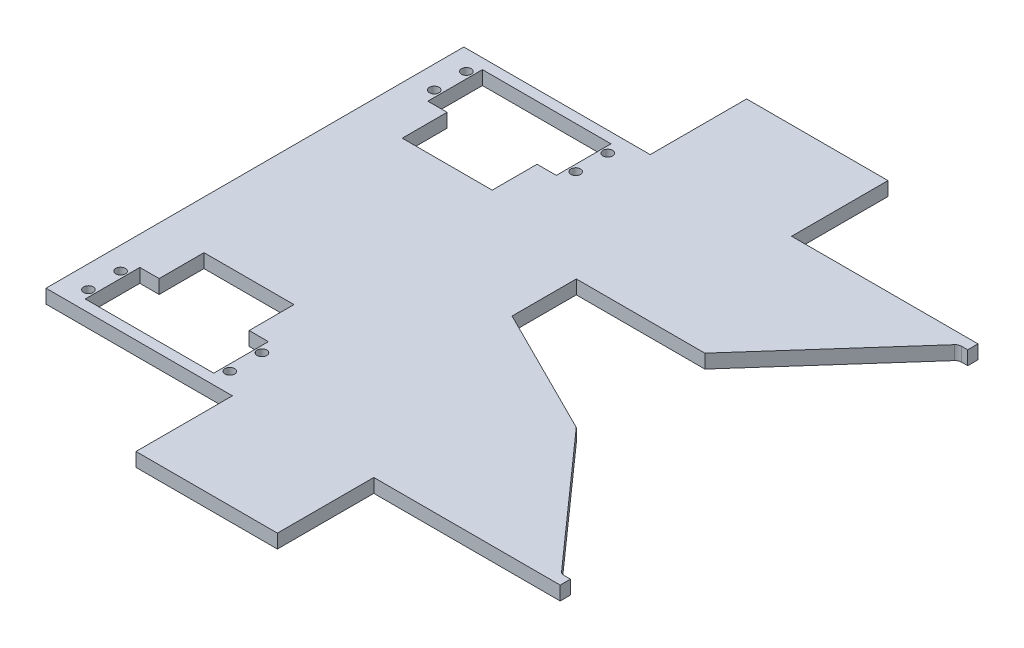
SolidWorks part; units mm, degrees
ref_plane "Front Plane" through (0, 0, 0) normal (0, 0, 1) x (1, 0, 0)
ref_plane "Top Plane" through (0, 0, 0) normal (0, 1, 0) x (1, 0, 0)
ref_plane "Right Plane" through (0, 0, 0) normal (1, 0, 0) x (0, 0, -1)
sketch "Sketch2" plane through (0, 0, 0) normal (0, 1, 0) x (1, 0, 0)
  line L2 (0, 0) -> (0, 65)
  line L3 (0, 65) -> (58, 65)
  line L4 (160, 0) -> (160, 65)
  line L8 (0, 0) -> (160, 0)
  line L9 (102, 65) -> (160, 65)
  line L11 (102, 65) -> (102, 95)
  line L12 (58, 65) -> (58, 95)
  line L13 (58, 95) -> (102, 95)
  dimension "D1" = 65
  dimension "D2" = 160
  dimension "D3" = 44
  dimension "D4" = 30
extrude "Boss-Extrude1" add sketch "Sketch2" along normal blind 4.3
mirror "Mirror1" about plane through (0, 4.3, 0) normal (0, 0, -1) of bodies 101
sketch "Sketch3" plane through (0, 4.3, 0) normal (0, 1, 0) x (1, 0, 0)
  line L0 (160, 61.8) -> (160, -61.8)
  line L1 (120.0126, 20) -> (157.1565, 61.8)
  line L3 (80.0126, 0) -> (80.0126, 20)
  line L4 (80.0126, 20) -> (120.0126, 20)
  line L12 (160, 65) -> (102, 65)
  line L13 (102, 65) -> (102, 95)
  line L15 (102, 95) -> (58, 95)
  line L16 (58, 65) -> (0, 65)
  line L17 (0, 65) -> (0, -65)
  line L18 (0, -65) -> (58, -65)
  line L20 (58, 95) -> (58, 65)
  line L22 (102, -65) -> (160, -65)
  line L23 (160, -65) -> (160, 65)
  line L36 (58, -65) -> (58, -95)
  line L38 (58, -95) -> (102, -95)
  line L39 (58, -95) -> (102, -95)
  line L40 (102, -95) -> (102, -65)
  line L42 (160, -61.8) -> (157.1556, -61.8)
  line L45 (160, 61.8) -> (157.1565, 61.8)
  line L48 (80.0126, 0) -> (120, -20)
  line L49 (120, -20) -> (157.1556, -61.8)
  line M24 (160, -65) -> (160, 65)
  dimension "D2" = 130
  dimension "D3" = 20
  dimension "D4" = 40
  dimension "D1" = 0
extrude "Cut-Extrude1" cut sketch "Sketch3" against normal blind 4.5 contours L48 L49 L1 L4 L3 M24 region at (132.7054, 4.3, -1.1594)
fillet "Fillet1" radius 2 2 edges at (157.1565, 2.15, -61.8) (157.1556, 2.15, 61.8)
ref_axis "Axis1" through (80, 4.3, 95) along (0, 0, -1)
sketch "Sketch4" plane through (0, 4.3, 0) normal (0, 1, 0) x (1, 0, 0)
  line L0 (80, -95) -> (80, 95)
  line L1 (102, -95) -> (58, -95) construction
  line L2 (102, 95) -> (58, 95) construction
ref_plane "Plane2" through (0, 4.3, 0) normal (0, 1, 0) x (1, 0, 0)
sketch "Sketch6" plane through (0, 4.3, 0) normal (0, 1, 0) x (1, 0, 0)
  line L3 (9, -61.8) -> (49, -61.8)
  line L6 (29, -45.8) -> (29, -44.8)
  line L7 (9, -44.8) -> (15, -44.8)
  line L11 (43, -44.8) -> (43, -30.8418)
  line L12 (15, -44.8) -> (15, -30.8418)
  line L13 (15, -30.8418) -> (43, -30.8418)
  line L15 (0, 0) -> (80.0126, 0)
  line L16 (80.0126, 0) -> (120, -20) construction
  line L18 (9, 44.8) -> (15, 44.8)
  line L20 (15, 30.8418) -> (43, 30.8418)
  line L21 (15, 44.8) -> (15, 30.8418)
  line L22 (43, 44.8) -> (43, 30.8418)
  line L25 (15, -45.8) -> (15, -30.8418) construction
  line L27 (9, 61.8) -> (49, 61.8)
  line L30 (4, -61.8) -> (3, -61.8)
  line L31 (0, -61.8) -> (160, -61.8) construction
  line L32 (3, -61.8) -> (4, -61.8)
  line L33 (3, -44.8) -> (3, -62.8) construction
  line L34 (3, -62.8) -> (55, -62.8) construction
  line L35 (55, -44.8) -> (55, -62.8) construction
  line L36 (4, -61.8) -> (54, -61.8) construction
  line L37 (0, 61.8) -> (160, 61.8) construction
  line L38 (54, 61.8) -> (55, 61.8)
  line L39 (54, 61.8) -> (55, 61.8)
  line L40 (43, 44.8) -> (49, 44.8)
  line L41 (4, -45.8) -> (4, -61.8) construction
  line L42 (4, -45.8) -> (54, -45.8) construction
  line L43 (43, -44.8) -> (49, -44.8)
  line L44 (3, -44.8) -> (55, -44.8) construction
  line L45 (29, -45.8) -> (29, -30.8418) construction
  line L46 (43, -45.8) -> (43, -30.8418) construction
  line L47 (54, -45.8) -> (54, -61.8) construction
  line L48 (9, -61.8) -> (49, -61.8)
  line L52 (9, 61.8) -> (9, 44.8)
  line L53 (55, 61.8) -> (54, 61.8)
  line L56 (49, 61.8) -> (49, 44.8)
  line L59 (3, -61.8) -> (4, -61.8)
  line L60 (9, -44.8) -> (9, -61.8)
  line L64 (49, -44.8) -> (49, -61.8)
  dimension "D4" = 1
  dimension "D5" = 14
  dimension "D6" = 14
extrude "Cut-Extrude2" cut sketch "Sketch6" against normal blind 10
sketch "Sketch7" plane through (0, 4.3, 0) normal (0, 1, 0) x (1, 0, 0)
  line L0 (0, 0) -> (80.0126, 0)
  line L1 (0, 65) -> (0, -65) construction
sketch "Sketch8" plane through (0, 4.3, 0) normal (0, 1, 0) x (1, 0, 0)
  circle A0 centre (7, 58.8) radius 1.5
  circle A1 centre (7, 48.8) radius 1.5
  circle A2 centre (51, 48.8) radius 1.5
  circle A3 centre (51, 58.8) radius 1.5
  circle A4 centre (7, -48.8) radius 1.5
  circle A5 centre (7, -58.8) radius 1.5
  circle A6 centre (51, -58.8) radius 1.5
  circle A7 centre (51, -48.8) radius 1.5
  dimension "D7" = 3
extrude "Cut-Extrude3" cut sketch "Sketch8" against normal blind 10
